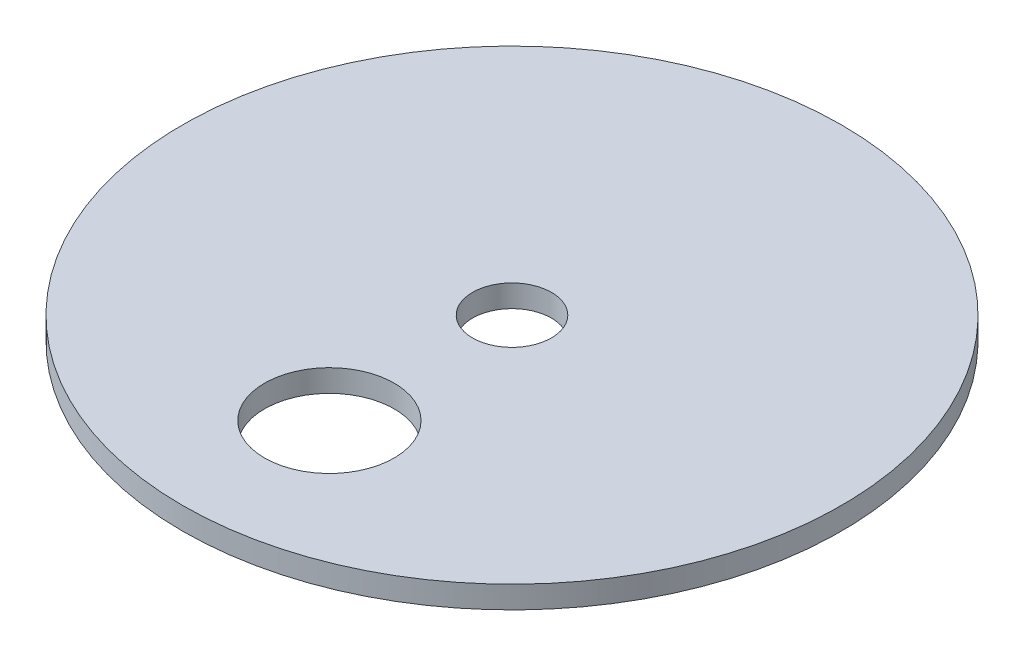
SolidWorks part; units mm, degrees
material "PVC Rigid"
ref_plane "Front" through (0, 0, 0) normal (0, 0, 1) x (1, 0, 0)
ref_plane "Top" through (0, 0, 0) normal (0, 1, 0) x (1, 0, 0)
ref_plane "Right" through (0, 0, 0) normal (1, 0, 0) x (0, 0, -1)
sketch "Sketch1" plane through (0, 0, 0) normal (0, 1, 0) x (1, 0, 0)
  circle A0 centre (0, 0) radius 44.375
  dimension "D1" = 88.75
extrude "Boss-Extrude1" add sketch "Sketch1" along normal blind 3
sketch "Sketch2" plane through (0, 0, 0) normal (0, 1, 0) x (1, 0, 0)
  circle A0 centre (0, 0) radius 5.3155
  circle A1 centre (0, -24.5888) radius 8.7297
extrude "Cut-Extrude2" cut sketch "Sketch2" against normal blind 3 and the other way blind 13
